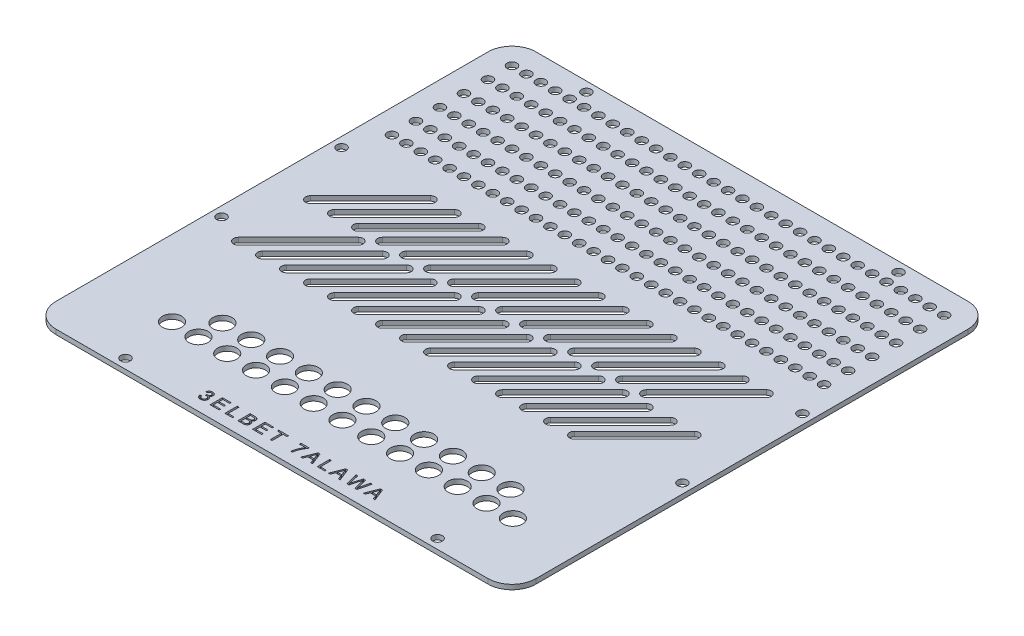
SolidWorks part; units mm, degrees
ref_plane "Front Plane" through (0, 0, 0) normal (0, 0, 1) x (1, 0, 0)
ref_plane "Top Plane" through (0, 0, 0) normal (0, 1, 0) x (1, 0, 0)
ref_plane "Right Plane" through (0, 0, 0) normal (1, 0, 0) x (0, 0, -1)
sketch "Sketch2" plane through (0, 0, 0) normal (0, 1, 0) x (1, 0, 0)
  line L0 (-83.7203, -0.2797) -> (-58.7203, 24.7203) construction
  line L1 (-90, -100) -> (90, -100)
  line L2 (-100, -90) -> (-100, 90)
  line L3 (-90, 100) -> (90, 100)
  line L4 (100, -90) -> (100, 90)
  line L5 (-100, -100) -> (100, 100) construction
  line L6 (-100, 100) -> (100, -100) construction
  line L7 (-85.1345, 1.1345) -> (-60.1345, 26.1345)
  line L8 (-82.3061, -1.6939) -> (-57.3061, 23.3061)
  line L9 (-73.7203, -0.2797) -> (-48.7203, 24.7203) construction
  line L10 (-75.1345, 1.1345) -> (-50.1345, 26.1345)
  line L11 (-72.3061, -1.6939) -> (-47.3061, 23.3061)
  line L12 (-63.7203, -0.2797) -> (-38.7203, 24.7203) construction
  line L13 (-65.1345, 1.1345) -> (-40.1345, 26.1345)
  line L14 (-62.3061, -1.6939) -> (-37.3061, 23.3061)
  line L15 (-53.7203, -0.2797) -> (-28.7203, 24.7203) construction
  line L16 (-55.1345, 1.1345) -> (-30.1345, 26.1345)
  line L17 (-52.3061, -1.6939) -> (-27.3061, 23.3061)
  line L18 (-43.7203, -0.2797) -> (-18.7203, 24.7203) construction
  line L19 (-45.1345, 1.1345) -> (-20.1345, 26.1345)
  line L20 (-42.3061, -1.6939) -> (-17.3061, 23.3061)
  line L21 (-33.7203, -0.2797) -> (-8.7203, 24.7203) construction
  line L22 (-35.1345, 1.1345) -> (-10.1345, 26.1345)
  line L23 (-32.3061, -1.6939) -> (-7.3061, 23.3061)
  line L24 (-23.7203, -0.2797) -> (1.2797, 24.7203) construction
  line L25 (-25.1345, 1.1345) -> (-0.1345, 26.1345)
  line L26 (-22.3061, -1.6939) -> (2.6939, 23.3061)
  line L27 (-13.7203, -0.2797) -> (11.2797, 24.7203) construction
  line L28 (-15.1345, 1.1345) -> (9.8655, 26.1345)
  line L29 (-12.3061, -1.6939) -> (12.6939, 23.3061)
  line L30 (-3.7203, -0.2797) -> (21.2797, 24.7203) construction
  line L31 (-5.1345, 1.1345) -> (19.8655, 26.1345)
  line L32 (-2.3061, -1.6939) -> (22.6939, 23.3061)
  line L33 (6.2797, -0.2797) -> (31.2797, 24.7203) construction
  line L34 (4.8655, 1.1345) -> (29.8655, 26.1345)
  line L35 (7.6939, -1.6939) -> (32.6939, 23.3061)
  line L36 (16.2797, -0.2797) -> (41.2797, 24.7203) construction
  line L37 (14.8655, 1.1345) -> (39.8655, 26.1345)
  line L38 (17.6939, -1.6939) -> (42.6939, 23.3061)
  line L39 (26.2797, -0.2797) -> (51.2797, 24.7203) construction
  line L40 (24.8655, 1.1345) -> (49.8655, 26.1345)
  line L41 (27.6939, -1.6939) -> (52.6939, 23.3061)
  line L42 (36.2797, -0.2797) -> (61.2797, 24.7203) construction
  line L43 (34.8655, 1.1345) -> (59.8655, 26.1345)
  line L44 (37.6939, -1.6939) -> (62.6939, 23.3061)
  line L45 (46.2797, -0.2797) -> (71.2797, 24.7203) construction
  line L46 (44.8655, 1.1345) -> (69.8655, 26.1345)
  line L47 (47.6939, -1.6939) -> (72.6939, 23.3061)
  line L48 (56.2797, -0.2797) -> (81.2797, 24.7203) construction
  line L49 (54.8655, 1.1345) -> (79.8655, 26.1345)
  line L50 (57.6939, -1.6939) -> (82.6939, 23.3061)
  line L51 (-73.7203, -30.2797) -> (-48.7203, -5.2797) construction
  line L52 (-75.1345, -28.8655) -> (-50.1345, -3.8655)
  line L53 (-72.3061, -31.6939) -> (-47.3061, -6.6939)
  line L54 (-63.7203, -30.2797) -> (-38.7203, -5.2797) construction
  line L55 (-65.1345, -28.8655) -> (-40.1345, -3.8655)
  line L56 (-62.3061, -31.6939) -> (-37.3061, -6.6939)
  line L57 (-53.7203, -30.2797) -> (-28.7203, -5.2797) construction
  line L58 (-55.1345, -28.8655) -> (-30.1345, -3.8655)
  line L59 (-52.3061, -31.6939) -> (-27.3061, -6.6939)
  line L60 (-43.7203, -30.2797) -> (-18.7203, -5.2797) construction
  line L61 (-45.1345, -28.8655) -> (-20.1345, -3.8655)
  line L62 (-42.3061, -31.6939) -> (-17.3061, -6.6939)
  line L63 (-33.7203, -30.2797) -> (-8.7203, -5.2797) construction
  line L64 (-35.1345, -28.8655) -> (-10.1345, -3.8655)
  line L65 (-32.3061, -31.6939) -> (-7.3061, -6.6939)
  line L66 (-23.7203, -30.2797) -> (1.2797, -5.2797) construction
  line L67 (-25.1345, -28.8655) -> (-0.1345, -3.8655)
  line L68 (-22.3061, -31.6939) -> (2.6939, -6.6939)
  line L69 (-13.7203, -30.2797) -> (11.2797, -5.2797) construction
  line L70 (-15.1345, -28.8655) -> (9.8655, -3.8655)
  line L71 (-12.3061, -31.6939) -> (12.6939, -6.6939)
  line L72 (-3.7203, -30.2797) -> (21.2797, -5.2797) construction
  line L73 (-5.1345, -28.8655) -> (19.8655, -3.8655)
  line L74 (-2.3061, -31.6939) -> (22.6939, -6.6939)
  line L75 (6.2797, -30.2797) -> (31.2797, -5.2797) construction
  line L76 (4.8655, -28.8655) -> (29.8655, -3.8655)
  line L77 (7.6939, -31.6939) -> (32.6939, -6.6939)
  line L78 (16.2797, -30.2797) -> (41.2797, -5.2797) construction
  line L79 (14.8655, -28.8655) -> (39.8655, -3.8655)
  line L80 (17.6939, -31.6939) -> (42.6939, -6.6939)
  line L81 (26.2797, -30.2797) -> (51.2797, -5.2797) construction
  line L82 (24.8655, -28.8655) -> (49.8655, -3.8655)
  line L83 (27.6939, -31.6939) -> (52.6939, -6.6939)
  line L84 (36.2797, -30.2797) -> (61.2797, -5.2797) construction
  line L85 (34.8655, -28.8655) -> (59.8655, -3.8655)
  line L86 (37.6939, -31.6939) -> (62.6939, -6.6939)
  line L87 (46.2797, -30.2797) -> (71.2797, -5.2797) construction
  line L88 (44.8655, -28.8655) -> (69.8655, -3.8655)
  line L89 (47.6939, -31.6939) -> (72.6939, -6.6939)
  line L90 (56.2797, -30.2797) -> (81.2797, -5.2797) construction
  line L91 (54.8655, -28.8655) -> (79.8655, -3.8655)
  line L92 (57.6939, -31.6939) -> (82.6939, -6.6939)
  line L93 (-83.7203, -30.2797) -> (-58.7203, -5.2797) construction
  line L94 (-85.1345, -28.8655) -> (-60.1345, -3.8655)
  line L95 (-82.3061, -31.6939) -> (-57.3061, -6.6939)
  circle A0 centre (-65, 96) radius 2
  circle A1 centre (65, 96) radius 2
  circle A2 centre (96, 25) radius 2
  circle A3 centre (96, -25) radius 2
  circle A4 centre (-96, 25) radius 2
  circle A5 centre (-96, -25) radius 2
  circle A6 centre (-65, -96) radius 2
  circle A7 centre (65, -96) radius 2
  arc A8 (-100, 90) -> (-90, 100) centre (-90, 90) cw
  arc A9 (-90, -100) -> (-100, -90) centre (-90, -90) cw
  arc A10 (90, -100) -> (100, -90) centre (90, -90) ccw
  arc A11 (90, 100) -> (100, 90) centre (90, 90) cw
  circle A12 centre (-90, 90) radius 2
  circle A13 centre (-84, 90) radius 2
  circle A14 centre (-78, 90) radius 2
  circle A15 centre (-72, 90) radius 2
  circle A16 centre (-66, 90) radius 2
  circle A17 centre (-60, 90) radius 2
  circle A18 centre (-54, 90) radius 2
  circle A19 centre (-48, 90) radius 2
  circle A20 centre (-42, 90) radius 2
  circle A21 centre (-36, 90) radius 2
  circle A22 centre (-30, 90) radius 2
  circle A23 centre (-24, 90) radius 2
  circle A24 centre (-18, 90) radius 2
  circle A25 centre (-12, 90) radius 2
  circle A26 centre (-6, 90) radius 2
  circle A27 centre (0, 90) radius 2
  circle A28 centre (6, 90) radius 2
  circle A29 centre (12, 90) radius 2
  circle A30 centre (18, 90) radius 2
  circle A31 centre (24, 90) radius 2
  circle A32 centre (30, 90) radius 2
  circle A33 centre (36, 90) radius 2
  circle A34 centre (42, 90) radius 2
  circle A35 centre (48, 90) radius 2
  circle A36 centre (54, 90) radius 2
  circle A37 centre (60, 90) radius 2
  circle A38 centre (66, 90) radius 2
  circle A39 centre (72, 90) radius 2
  circle A40 centre (78, 90) radius 2
  circle A41 centre (84, 90) radius 2
  circle A42 centre (90, 90) radius 2
  circle A43 centre (-84, 80) radius 2
  circle A44 centre (-78, 80) radius 2
  circle A45 centre (-72, 80) radius 2
  circle A46 centre (-66, 80) radius 2
  circle A47 centre (-60, 80) radius 2
  circle A48 centre (-54, 80) radius 2
  circle A49 centre (-48, 80) radius 2
  circle A50 centre (-42, 80) radius 2
  circle A51 centre (-36, 80) radius 2
  circle A52 centre (-30, 80) radius 2
  circle A53 centre (-24, 80) radius 2
  circle A54 centre (-18, 80) radius 2
  circle A55 centre (-12, 80) radius 2
  circle A56 centre (-6, 80) radius 2
  circle A57 centre (0, 80) radius 2
  circle A58 centre (6, 80) radius 2
  circle A59 centre (12, 80) radius 2
  circle A60 centre (18, 80) radius 2
  circle A61 centre (24, 80) radius 2
  circle A62 centre (30, 80) radius 2
  circle A63 centre (36, 80) radius 2
  circle A64 centre (42, 80) radius 2
  circle A65 centre (48, 80) radius 2
  circle A66 centre (54, 80) radius 2
  circle A67 centre (60, 80) radius 2
  circle A68 centre (66, 80) radius 2
  circle A69 centre (72, 80) radius 2
  circle A70 centre (78, 80) radius 2
  circle A71 centre (84, 80) radius 2
  circle A72 centre (90, 80) radius 2
  circle A73 centre (-84, 70) radius 2
  circle A74 centre (-78, 70) radius 2
  circle A75 centre (-72, 70) radius 2
  circle A76 centre (-66, 70) radius 2
  circle A77 centre (-60, 70) radius 2
  circle A78 centre (-54, 70) radius 2
  circle A79 centre (-48, 70) radius 2
  circle A80 centre (-42, 70) radius 2
  circle A81 centre (-36, 70) radius 2
  circle A82 centre (-30, 70) radius 2
  circle A83 centre (-24, 70) radius 2
  circle A84 centre (-18, 70) radius 2
  circle A85 centre (-12, 70) radius 2
  circle A86 centre (-6, 70) radius 2
  circle A87 centre (0, 70) radius 2
  circle A88 centre (6, 70) radius 2
  circle A89 centre (12, 70) radius 2
  circle A90 centre (18, 70) radius 2
  circle A91 centre (24, 70) radius 2
  circle A92 centre (30, 70) radius 2
  circle A93 centre (36, 70) radius 2
  circle A94 centre (42, 70) radius 2
  circle A95 centre (48, 70) radius 2
  circle A96 centre (54, 70) radius 2
  circle A97 centre (60, 70) radius 2
  circle A98 centre (66, 70) radius 2
  circle A99 centre (72, 70) radius 2
  circle A100 centre (78, 70) radius 2
  circle A101 centre (84, 70) radius 2
  circle A102 centre (90, 70) radius 2
  circle A103 centre (-84, 60) radius 2
  circle A104 centre (-78, 60) radius 2
  circle A105 centre (-72, 60) radius 2
  circle A106 centre (-66, 60) radius 2
  circle A107 centre (-60, 60) radius 2
  circle A108 centre (-54, 60) radius 2
  circle A109 centre (-48, 60) radius 2
  circle A110 centre (-42, 60) radius 2
  circle A111 centre (-36, 60) radius 2
  circle A112 centre (-30, 60) radius 2
  circle A113 centre (-24, 60) radius 2
  circle A114 centre (-18, 60) radius 2
  circle A115 centre (-12, 60) radius 2
  circle A116 centre (-6, 60) radius 2
  circle A117 centre (0, 60) radius 2
  circle A118 centre (6, 60) radius 2
  circle A119 centre (12, 60) radius 2
  circle A120 centre (18, 60) radius 2
  circle A121 centre (24, 60) radius 2
  circle A122 centre (30, 60) radius 2
  circle A123 centre (36, 60) radius 2
  circle A124 centre (42, 60) radius 2
  circle A125 centre (48, 60) radius 2
  circle A126 centre (54, 60) radius 2
  circle A127 centre (60, 60) radius 2
  circle A128 centre (66, 60) radius 2
  circle A129 centre (72, 60) radius 2
  circle A130 centre (78, 60) radius 2
  circle A131 centre (84, 60) radius 2
  circle A132 centre (90, 60) radius 2
  circle A133 centre (-84, 50) radius 2
  circle A134 centre (-78, 50) radius 2
  circle A135 centre (-72, 50) radius 2
  circle A136 centre (-66, 50) radius 2
  circle A137 centre (-60, 50) radius 2
  circle A138 centre (-54, 50) radius 2
  circle A139 centre (-48, 50) radius 2
  circle A140 centre (-42, 50) radius 2
  circle A141 centre (-36, 50) radius 2
  circle A142 centre (-30, 50) radius 2
  circle A143 centre (-24, 50) radius 2
  circle A144 centre (-18, 50) radius 2
  circle A145 centre (-12, 50) radius 2
  circle A146 centre (-6, 50) radius 2
  circle A147 centre (0, 50) radius 2
  circle A148 centre (6, 50) radius 2
  circle A149 centre (12, 50) radius 2
  circle A150 centre (18, 50) radius 2
  circle A151 centre (24, 50) radius 2
  circle A152 centre (30, 50) radius 2
  circle A153 centre (36, 50) radius 2
  circle A154 centre (42, 50) radius 2
  circle A155 centre (48, 50) radius 2
  circle A156 centre (54, 50) radius 2
  circle A157 centre (60, 50) radius 2
  circle A158 centre (66, 50) radius 2
  circle A159 centre (72, 50) radius 2
  circle A160 centre (78, 50) radius 2
  circle A161 centre (84, 50) radius 2
  circle A162 centre (90, 50) radius 2
  circle A163 centre (-84, 40) radius 2
  circle A164 centre (-78, 40) radius 2
  circle A165 centre (-72, 40) radius 2
  circle A166 centre (-66, 40) radius 2
  circle A167 centre (-60, 40) radius 2
  circle A168 centre (-54, 40) radius 2
  circle A169 centre (-48, 40) radius 2
  circle A170 centre (-42, 40) radius 2
  circle A171 centre (-36, 40) radius 2
  circle A172 centre (-30, 40) radius 2
  circle A173 centre (-24, 40) radius 2
  circle A174 centre (-18, 40) radius 2
  circle A175 centre (-12, 40) radius 2
  circle A176 centre (-6, 40) radius 2
  circle A177 centre (0, 40) radius 2
  circle A178 centre (6, 40) radius 2
  circle A179 centre (12, 40) radius 2
  circle A180 centre (18, 40) radius 2
  circle A181 centre (24, 40) radius 2
  circle A182 centre (30, 40) radius 2
  circle A183 centre (36, 40) radius 2
  circle A184 centre (42, 40) radius 2
  circle A185 centre (48, 40) radius 2
  circle A186 centre (54, 40) radius 2
  circle A187 centre (60, 40) radius 2
  circle A188 centre (66, 40) radius 2
  circle A189 centre (72, 40) radius 2
  circle A190 centre (78, 40) radius 2
  circle A191 centre (84, 40) radius 2
  circle A192 centre (90, 40) radius 2
  circle A193 centre (-57.4813, -63.1381) radius 4
  circle A194 centre (-45.4813, -63.1381) radius 4
  circle A195 centre (-33.4813, -63.1381) radius 4
  circle A196 centre (-21.4813, -63.1381) radius 4
  circle A197 centre (-9.4813, -63.1381) radius 4
  circle A198 centre (2.5187, -63.1381) radius 4
  circle A199 centre (14.5187, -63.1381) radius 4
  circle A200 centre (26.5187, -63.1381) radius 4
  circle A201 centre (38.5187, -63.1381) radius 4
  circle A202 centre (50.5187, -63.1381) radius 4
  circle A203 centre (62.5187, -63.1381) radius 4
  circle A204 centre (-45.4813, -73.1381) radius 4
  circle A205 centre (-33.4813, -73.1381) radius 4
  circle A206 centre (-21.4813, -73.1381) radius 4
  circle A207 centre (-9.4813, -73.1381) radius 4
  circle A208 centre (2.5187, -73.1381) radius 4
  circle A209 centre (14.5187, -73.1381) radius 4
  circle A210 centre (26.5187, -73.1381) radius 4
  circle A211 centre (38.5187, -73.1381) radius 4
  circle A212 centre (50.5187, -73.1381) radius 4
  circle A213 centre (62.5187, -73.1381) radius 4
  circle A214 centre (-57.4813, -73.1381) radius 4
  circle A215 centre (-68.4813, -73.1381) radius 4
  circle A216 centre (73.5187, -73.1381) radius 4
  arc A223 (-85.1345, 1.1345) -> (-82.3061, -1.6939) centre (-83.7203, -0.2797) ccw
  arc A224 (-57.3061, 23.3061) -> (-60.1345, 26.1345) centre (-58.7203, 24.7203) ccw
  arc A225 (-75.1345, 1.1345) -> (-72.3061, -1.6939) centre (-73.7203, -0.2797) ccw
  arc A226 (-47.3061, 23.3061) -> (-50.1345, 26.1345) centre (-48.7203, 24.7203) ccw
  arc A227 (-65.1345, 1.1345) -> (-62.3061, -1.6939) centre (-63.7203, -0.2797) ccw
  arc A228 (-37.3061, 23.3061) -> (-40.1345, 26.1345) centre (-38.7203, 24.7203) ccw
  arc A229 (-55.1345, 1.1345) -> (-52.3061, -1.6939) centre (-53.7203, -0.2797) ccw
  arc A230 (-27.3061, 23.3061) -> (-30.1345, 26.1345) centre (-28.7203, 24.7203) ccw
  arc A231 (-45.1345, 1.1345) -> (-42.3061, -1.6939) centre (-43.7203, -0.2797) ccw
  arc A232 (-17.3061, 23.3061) -> (-20.1345, 26.1345) centre (-18.7203, 24.7203) ccw
  arc A233 (-35.1345, 1.1345) -> (-32.3061, -1.6939) centre (-33.7203, -0.2797) ccw
  arc A234 (-7.3061, 23.3061) -> (-10.1345, 26.1345) centre (-8.7203, 24.7203) ccw
  arc A235 (-25.1345, 1.1345) -> (-22.3061, -1.6939) centre (-23.7203, -0.2797) ccw
  arc A236 (2.6939, 23.3061) -> (-0.1345, 26.1345) centre (1.2797, 24.7203) ccw
  arc A237 (-15.1345, 1.1345) -> (-12.3061, -1.6939) centre (-13.7203, -0.2797) ccw
  arc A238 (12.6939, 23.3061) -> (9.8655, 26.1345) centre (11.2797, 24.7203) ccw
  arc A239 (-5.1345, 1.1345) -> (-2.3061, -1.6939) centre (-3.7203, -0.2797) ccw
  arc A240 (22.6939, 23.3061) -> (19.8655, 26.1345) centre (21.2797, 24.7203) ccw
  arc A241 (4.8655, 1.1345) -> (7.6939, -1.6939) centre (6.2797, -0.2797) ccw
  arc A242 (32.6939, 23.3061) -> (29.8655, 26.1345) centre (31.2797, 24.7203) ccw
  arc A243 (14.8655, 1.1345) -> (17.6939, -1.6939) centre (16.2797, -0.2797) ccw
  arc A244 (42.6939, 23.3061) -> (39.8655, 26.1345) centre (41.2797, 24.7203) ccw
  arc A245 (24.8655, 1.1345) -> (27.6939, -1.6939) centre (26.2797, -0.2797) ccw
  arc A246 (52.6939, 23.3061) -> (49.8655, 26.1345) centre (51.2797, 24.7203) ccw
  arc A247 (34.8655, 1.1345) -> (37.6939, -1.6939) centre (36.2797, -0.2797) ccw
  arc A248 (62.6939, 23.3061) -> (59.8655, 26.1345) centre (61.2797, 24.7203) ccw
  arc A249 (44.8655, 1.1345) -> (47.6939, -1.6939) centre (46.2797, -0.2797) ccw
  arc A250 (72.6939, 23.3061) -> (69.8655, 26.1345) centre (71.2797, 24.7203) ccw
  arc A251 (54.8655, 1.1345) -> (57.6939, -1.6939) centre (56.2797, -0.2797) ccw
  arc A252 (82.6939, 23.3061) -> (79.8655, 26.1345) centre (81.2797, 24.7203) ccw
  circle A253 centre (-90, 80) radius 2
  circle A254 centre (-90, 70) radius 2
  circle A255 centre (-90, 60) radius 2
  circle A256 centre (-90, 50) radius 2
  circle A257 centre (-90, 40) radius 2
  arc A259 (-75.1345, -28.8655) -> (-72.3061, -31.6939) centre (-73.7203, -30.2797) ccw
  circle A260 centre (-84, 20) radius 2 [skipped]
  circle A261 centre (-78, 20) radius 2 [skipped]
  circle A262 centre (-72, 20) radius 2 [skipped]
  circle A263 centre (-66, 20) radius 2 [skipped]
  circle A264 centre (-60, 20) radius 2 [skipped]
  circle A265 centre (-54, 20) radius 2 [skipped]
  circle A266 centre (-48, 20) radius 2 [skipped]
  circle A267 centre (-42, 20) radius 2 [skipped]
  circle A268 centre (-36, 20) radius 2 [skipped]
  circle A269 centre (-30, 20) radius 2 [skipped]
  circle A270 centre (-24, 20) radius 2 [skipped]
  circle A271 centre (-18, 20) radius 2 [skipped]
  circle A272 centre (-12, 20) radius 2 [skipped]
  circle A273 centre (-6, 20) radius 2 [skipped]
  circle A274 centre (0, 20) radius 2 [skipped]
  circle A275 centre (6, 20) radius 2 [skipped]
  circle A276 centre (12, 20) radius 2 [skipped]
  circle A277 centre (18, 20) radius 2 [skipped]
  circle A278 centre (24, 20) radius 2 [skipped]
  circle A279 centre (30, 20) radius 2 [skipped]
  circle A280 centre (36, 20) radius 2 [skipped]
  circle A281 centre (42, 20) radius 2 [skipped]
  circle A282 centre (48, 20) radius 2 [skipped]
  circle A283 centre (54, 20) radius 2 [skipped]
  circle A284 centre (60, 20) radius 2 [skipped]
  circle A285 centre (66, 20) radius 2 [skipped]
  circle A286 centre (72, 20) radius 2 [skipped]
  circle A287 centre (78, 20) radius 2 [skipped]
  circle A288 centre (84, 20) radius 2 [skipped]
  circle A289 centre (90, 20) radius 2 [skipped]
  circle A290 centre (-90, 20) radius 2 [skipped]
  arc A291 (-47.3061, -6.6939) -> (-50.1345, -3.8655) centre (-48.7203, -5.2797) ccw
  arc A292 (-65.1345, -28.8655) -> (-62.3061, -31.6939) centre (-63.7203, -30.2797) ccw
  arc A293 (-37.3061, -6.6939) -> (-40.1345, -3.8655) centre (-38.7203, -5.2797) ccw
  arc A294 (-55.1345, -28.8655) -> (-52.3061, -31.6939) centre (-53.7203, -30.2797) ccw
  arc A295 (-27.3061, -6.6939) -> (-30.1345, -3.8655) centre (-28.7203, -5.2797) ccw
  arc A296 (-45.1345, -28.8655) -> (-42.3061, -31.6939) centre (-43.7203, -30.2797) ccw
  arc A297 (-17.3061, -6.6939) -> (-20.1345, -3.8655) centre (-18.7203, -5.2797) ccw
  arc A298 (-35.1345, -28.8655) -> (-32.3061, -31.6939) centre (-33.7203, -30.2797) ccw
  arc A299 (-7.3061, -6.6939) -> (-10.1345, -3.8655) centre (-8.7203, -5.2797) ccw
  arc A300 (-25.1345, -28.8655) -> (-22.3061, -31.6939) centre (-23.7203, -30.2797) ccw
  arc A301 (2.6939, -6.6939) -> (-0.1345, -3.8655) centre (1.2797, -5.2797) ccw
  arc A302 (-15.1345, -28.8655) -> (-12.3061, -31.6939) centre (-13.7203, -30.2797) ccw
  arc A303 (12.6939, -6.6939) -> (9.8655, -3.8655) centre (11.2797, -5.2797) ccw
  arc A304 (-5.1345, -28.8655) -> (-2.3061, -31.6939) centre (-3.7203, -30.2797) ccw
  arc A305 (22.6939, -6.6939) -> (19.8655, -3.8655) centre (21.2797, -5.2797) ccw
  arc A306 (4.8655, -28.8655) -> (7.6939, -31.6939) centre (6.2797, -30.2797) ccw
  arc A307 (32.6939, -6.6939) -> (29.8655, -3.8655) centre (31.2797, -5.2797) ccw
  arc A308 (14.8655, -28.8655) -> (17.6939, -31.6939) centre (16.2797, -30.2797) ccw
  arc A309 (42.6939, -6.6939) -> (39.8655, -3.8655) centre (41.2797, -5.2797) ccw
  arc A310 (24.8655, -28.8655) -> (27.6939, -31.6939) centre (26.2797, -30.2797) ccw
  arc A311 (52.6939, -6.6939) -> (49.8655, -3.8655) centre (51.2797, -5.2797) ccw
  arc A312 (34.8655, -28.8655) -> (37.6939, -31.6939) centre (36.2797, -30.2797) ccw
  arc A313 (62.6939, -6.6939) -> (59.8655, -3.8655) centre (61.2797, -5.2797) ccw
  arc A314 (44.8655, -28.8655) -> (47.6939, -31.6939) centre (46.2797, -30.2797) ccw
  arc A315 (72.6939, -6.6939) -> (69.8655, -3.8655) centre (71.2797, -5.2797) ccw
  arc A316 (54.8655, -28.8655) -> (57.6939, -31.6939) centre (56.2797, -30.2797) ccw
  arc A317 (82.6939, -6.6939) -> (79.8655, -3.8655) centre (81.2797, -5.2797) ccw
  arc A318 (-85.1345, -28.8655) -> (-82.3061, -31.6939) centre (-83.7203, -30.2797) ccw
  arc A319 (-57.3061, -6.6939) -> (-60.1345, -3.8655) centre (-58.7203, -5.2797) ccw
  circle A320 centre (-84, 30) radius 2 [skipped]
  circle A321 centre (-78, 30) radius 2 [skipped]
  circle A322 centre (-72, 30) radius 2 [skipped]
  circle A323 centre (-66, 30) radius 2 [skipped]
  circle A324 centre (-60, 30) radius 2 [skipped]
  circle A325 centre (-54, 30) radius 2 [skipped]
  circle A326 centre (-48, 30) radius 2 [skipped]
  circle A327 centre (-42, 30) radius 2 [skipped]
  circle A328 centre (-36, 30) radius 2 [skipped]
  circle A329 centre (-30, 30) radius 2 [skipped]
  circle A330 centre (-24, 30) radius 2 [skipped]
  circle A331 centre (-18, 30) radius 2 [skipped]
  circle A332 centre (-12, 30) radius 2 [skipped]
  circle A333 centre (-6, 30) radius 2 [skipped]
  circle A334 centre (0, 30) radius 2 [skipped]
  circle A335 centre (6, 30) radius 2 [skipped]
  circle A336 centre (12, 30) radius 2 [skipped]
  circle A337 centre (18, 30) radius 2 [skipped]
  circle A338 centre (24, 30) radius 2 [skipped]
  circle A339 centre (30, 30) radius 2 [skipped]
  circle A340 centre (36, 30) radius 2 [skipped]
  circle A341 centre (42, 30) radius 2 [skipped]
  circle A342 centre (48, 30) radius 2 [skipped]
  circle A343 centre (54, 30) radius 2 [skipped]
  circle A344 centre (60, 30) radius 2 [skipped]
  circle A345 centre (66, 30) radius 2 [skipped]
  circle A346 centre (72, 30) radius 2 [skipped]
  circle A347 centre (78, 30) radius 2 [skipped]
  circle A348 centre (84, 30) radius 2 [skipped]
  circle A349 centre (90, 30) radius 2 [skipped]
  circle A350 centre (-90, 30) radius 2 [skipped]
  text T0 "3ELBET 7ALAWA" height in points 20
  point P0 (0, 0)
  point P457 (-71.2203, 12.2203)
  point P466 (-61.2203, 12.2203)
  point P473 (-51.2203, 12.2203)
  point P480 (-41.2203, 12.2203)
  point P487 (-31.2203, 12.2203)
  point P494 (-21.2203, 12.2203)
  point P501 (-11.2203, 12.2203)
  point P508 (-1.2203, 12.2203)
  point P515 (8.7797, 12.2203)
  point P596 (18.7797, 12.2203)
  point P603 (28.7797, 12.2203)
  point P610 (38.7797, 12.2203)
  point P617 (48.7797, 12.2203)
  point P624 (58.7797, 12.2203)
  point P631 (68.7797, 12.2203)
  point P638 (-61.2203, -17.7797)
  point P645 (-51.2203, -17.7797)
  point P652 (-41.2203, -17.7797)
  point P659 (-31.2203, -17.7797)
  point P666 (-21.2203, -17.7797)
  point P673 (-11.2203, -17.7797)
  point P680 (-1.2203, -17.7797)
  point P687 (8.7797, -17.7797)
  point P694 (18.7797, -17.7797)
  point P701 (28.7797, -17.7797)
  point P708 (38.7797, -17.7797)
  point P715 (48.7797, -17.7797)
  point P722 (58.7797, -17.7797)
  point P729 (68.7797, -17.7797)
  point P736 (-71.2203, -17.7797)
  dimension "D3" = 35
  dimension "D5" = 4
  dimension "D7" = 75
  dimension "D9" = 125
  dimension "D11" = 4
  dimension "D12" = 10
  dimension "D13" = 10
  dimension "D14" = 31
  dimension "D16" = 4
  dimension "D17" = 15
  dimension "D19" = 11
  dimension "D1" = 200
  dimension "D2" = 200
  dimension "D4" = 4
  dimension "D6" = 35
  dimension "D8" = 4
  dimension "D10" = 4
  dimension "D15" = 8
  dimension "D18" = 2
  dimension "D20" = 2
  dimension "D21" = 2
  dimension "D22" = 2
extrude "Boss-Extrude2" add sketch "Sketch2" along normal blind 2
